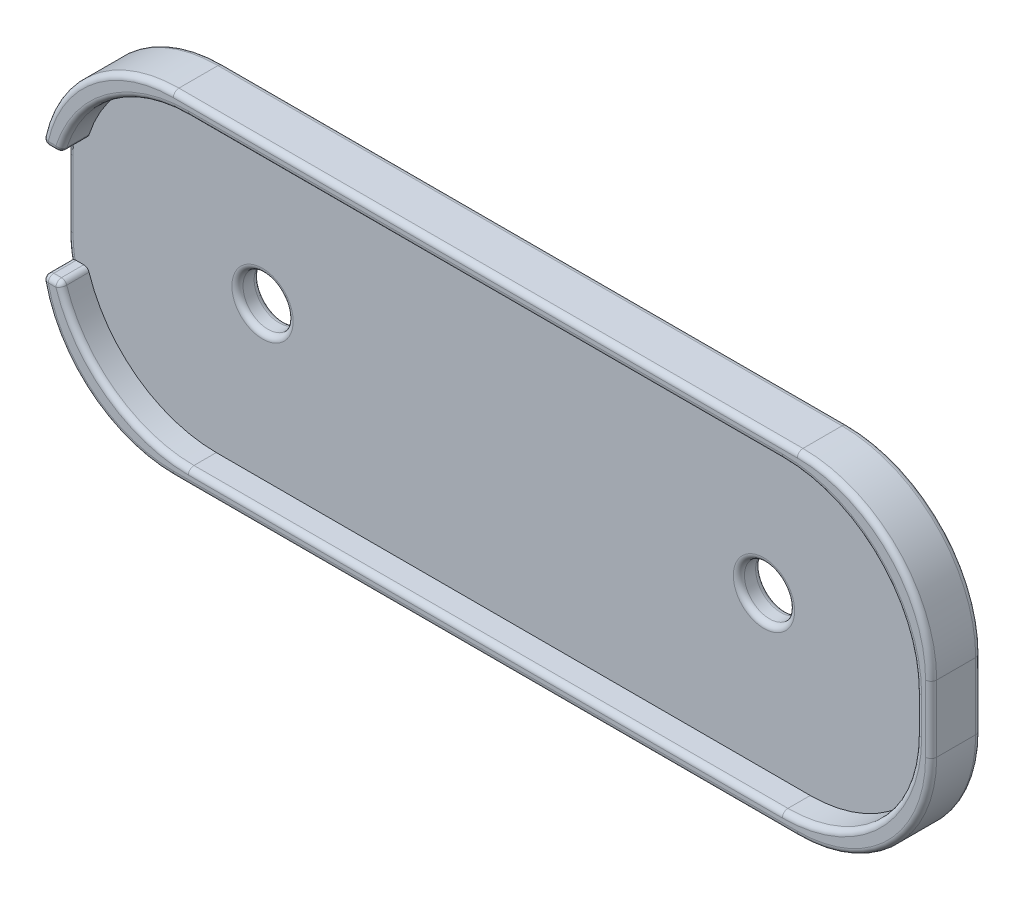
SolidWorks part; units mm, degrees
ref_plane "Front Plane" through (0, 0, 0) normal (0, 0, 1) x (1, 0, 0)
ref_plane "Top Plane" through (0, 0, 0) normal (0, 1, 0) x (1, 0, 0)
ref_plane "Right Plane" through (0, 0, 0) normal (1, 0, 0) x (0, 0, -1)
sketch "Sketch1" plane through (0, 0, 0) normal (0, 0, 1) x (1, 0, 0)
  line L1 (-40, 15) -> (40, 15)
  line L2 (-40, 15) -> (-40, -15)
  line L3 (-40, -15) -> (40, -15)
  line L4 (40, 15) -> (40, -15)
  line L5 (-40, 15) -> (40, -15) construction
  line L6 (-40, -15) -> (40, 15) construction
  point P0 (0, 0)
  dimension "D1" = 30
  dimension "D2" = 80
extrude "Boss-Extrude1" add sketch "Sketch1" along normal blind 2
sketch "Sketch2" plane through (0, 0, 2) normal (0, 0, 1) x (1, 0, 0)
  line L1 (-40, 15) -> (40, 15)
  line L2 (-40, 15) -> (-40, -15)
  line L3 (-40, -15) -> (40, -15)
  line L4 (40, 15) -> (40, -15)
  line L5 (38.65, 13.65) -> (-38.65, 13.65)
  line L6 (38.65, 13.65) -> (38.65, -13.65)
  line L7 (38.65, -13.65) -> (-38.65, -13.65)
  line L8 (-38.65, 13.65) -> (-38.65, -13.65)
  line L9 (38.65, 13.65) -> (-38.65, -13.65) construction
  line L10 (38.65, -13.65) -> (-38.65, 13.65) construction
  point P6 (0, 0)
  dimension "D1" = 1.35
  dimension "D2" = 1.35
extrude "Boss-Extrude2" add sketch "Sketch2" along normal blind 2.5
fillet "Fillet1" radius 12 8 edges at (-40, 15, 2.25) (40, 15, 2.25) (40, -15, 2.25) (-40, -15, 2.25) (38.65, -13.65, 3.25) (-38.65, -13.65, 3.25) (38.65, 13.65, 3.25) (-38.65, 13.65, 3.25)
sketch "Sketch3" plane through (0, 0, 2) normal (0, 0, 1) x (1, 0, 0)
  line L0 (-40, 3) -> (-40, -3) construction
  line L1 (-35, 5) -> (-45, 5)
  line L2 (-35, 5) -> (-35, -5)
  line L3 (-35, -5) -> (-45, -5)
  line L4 (-45, 5) -> (-45, -5)
  line L5 (-35, 5) -> (-45, -5) construction
  line L6 (-35, -5) -> (-45, 5) construction
  point P0 (-40, 0)
  dimension "D1" = 10
  dimension "D2" = 10
extrude "Cut-Extrude1" cut sketch "Sketch3" along normal through all
fillet "Fillet2" radius 0.5 31 edges at (0, -15, 0) (36.4853, -11.4853, 0) (40, 0, 0) (36.4853, 11.4853, 0) (0, 15, 0) (-36.4853, 11.4853, 0) (-40, 0, 0) (-39.958, -4.0035, 2) (-40, 0, 2) (-36.4853, -11.4853, 0) (-39.8322, -5, 3.25) (-38.1729, -5, 3.25) (-39.0025, -5, 4.5) (-38.1729, 5, 3.25) (-39.0025, 5, 4.5) (-39.8322, 5, 3.25) (-39.958, 4.0035, 2) (-33.8542, 11.2469, 4.5) (0, 13.65, 4.5) (-33.8542, -11.2469, 4.5) (0, -13.65, 4.5) (35.1353, -10.1353, 4.5) (38.65, 0, 4.5) (35.1353, 10.1353, 4.5) (-35.746, 12.1652, 4.5) (0, 15, 4.5) (36.4853, 11.4853, 4.5) (40, 0, 4.5) (36.4853, -11.4853, 4.5) (0, -15, 4.5) (-35.746, -12.1652, 4.5)
sketch "Sketch4" plane through (0, 0, 0) normal (0, 0, 1) x (1, 0, 0)
  line L0 (-22.5, 0) -> (22.5, 0) construction
  line L1 (-22.5, 0) -> (-40, 0) construction
  line L2 (-40, -3) -> (-40, 3) construction
  line L3 (22.5, 0) -> (40, 0) construction
  line L4 (40, 3) -> (40, -3) construction
  circle A0 centre (-22.5, 0) radius 2.25
  circle A1 centre (22.5, 0) radius 2.25
  point P11 (-24.2028, 0)
  dimension "D1" = 4.5
  dimension "D2" = 45
extrude "Cut-Extrude2" cut sketch "Sketch4" along normal through all
fillet "Fillet3" radius 0.5 4 edges at (24.75, 0, 0) (24.75, 0, 2) (-20.25, 0, 0) (-20.25, 0, 2)
